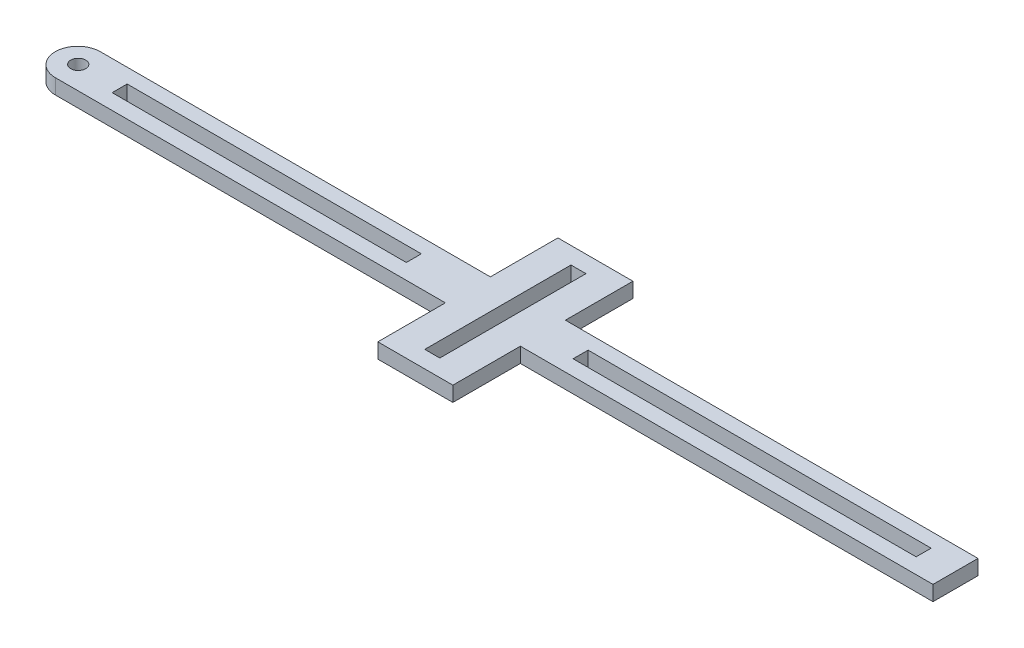
SolidWorks part; units mm, degrees
ref_plane "Front Plane" through (0, 0, 0) normal (0, 0, 1) x (1, 0, 0)
ref_plane "Top Plane" through (0, 0, 0) normal (0, 1, 0) x (1, 0, 0)
ref_plane "Right Plane" through (0, 0, 0) normal (1, 0, 0) x (0, 0, -1)
sketch "Sketch1" plane through (0, 0, 0) normal (0, 1, 0) x (1, 0, 0)
  line L0 (-5, 3) -> (-5, 12)
  line L1 (-60, -3) -> (-5, -3)
  line L2 (-60, -3) -> (-60, 3)
  line L3 (-60, 3) -> (-5, 3)
  line L4 (60, -3) -> (60, 3)
  line L5 (-60, -3) -> (60, 3) construction
  line L6 (-60, 3) -> (60, -3) construction
  line L7 (-5, -12) -> (5, -12)
  line L8 (-5, -12) -> (-5, -3)
  line L9 (-5, 12) -> (5, 12)
  line L10 (5, -12) -> (5, -3)
  line L11 (-5, -12) -> (5, 12) construction
  line L12 (-5, 12) -> (5, -12) construction
  line L13 (-12.2613, -0.9425) -> (-51.4746, -0.9425)
  line L14 (-12.2613, -0.9425) -> (-12.2613, 1.0575)
  line L15 (-12.2613, 1.0575) -> (-51.4746, 1.0575)
  line L16 (-51.4746, -0.9425) -> (-51.4746, 1.0575)
  line L17 (-12.2613, -0.9425) -> (-51.4746, 1.0575) construction
  line L18 (-12.2613, 1.0575) -> (-51.4746, -0.9425) construction
  line L19 (9.9693, -0.9425) -> (55.6961, -0.9425)
  line L20 (9.9693, -0.9425) -> (9.9693, 1.0575)
  line L21 (9.9693, 1.0575) -> (55.6961, 1.0575)
  line L22 (55.6961, -0.9425) -> (55.6961, 1.0575)
  line L23 (9.9693, -0.9425) -> (55.6961, 1.0575) construction
  line L24 (9.9693, 1.0575) -> (55.6961, -0.9425) construction
  line L26 (5, 3) -> (5, 12)
  line L27 (5, 3) -> (60, 3)
  line L28 (5, -3) -> (60, -3)
  line L29 (-1, -9.7423) -> (1, -9.7423)
  line L30 (-1, -9.7423) -> (-1, 9.7423)
  line L31 (-1, 9.7423) -> (1, 9.7423)
  line L32 (1, -9.7423) -> (1, 9.7423)
  line L33 (-1, -9.7423) -> (1, 9.7423) construction
  line L34 (-1, 9.7423) -> (1, -9.7423) construction
  circle A0 centre (-57, 0.0575) radius 1
  point P0 (0, 0)
  point P6 (0, 0)
  point P13 (-31.868, 0.0575)
  point P19 (32.8327, 0.0575)
  point P24 (0, 0)
  dimension "D5" = 2
  dimension "D1" = 120
  dimension "D2" = 10
  dimension "D3" = 6
  dimension "D4" = 24
  dimension "D6" = 2
  dimension "D7" = 3
  dimension "D8" = 2
  dimension "D9" = 2
extrude "Boss-Extrude1" add sketch "Sketch1" along normal blind 2
fillet "Fillet1" radius 3 2 edges at (-60, 1, 3) (-60, 1, -3)
